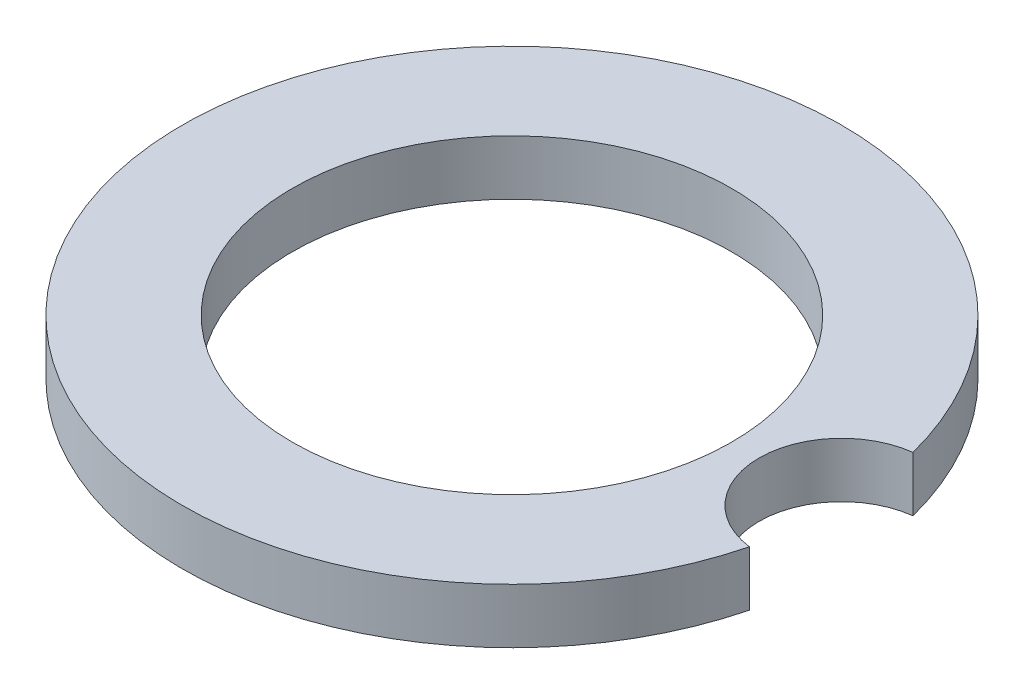
SolidWorks part; units mm, degrees
ref_plane "Front Plane" through (0, 0, 0) normal (0, 0, 1) x (1, 0, 0)
ref_plane "Top Plane" through (0, 0, 0) normal (0, 1, 0) x (1, 0, 0)
ref_plane "Right Plane" through (0, 0, 0) normal (1, 0, 0) x (0, 0, -1)
sketch "Sketch1" plane through (0, 0, 0) normal (0, 1, 0) x (1, 0, 0)
  circle A0 centre (0, 0) radius 50.8
  circle A1 centre (0, 0) radius 76.1746
  dimension "Front_CR_ID" = 101.6
  dimension "Front_CR_OD" = 152.3492
extrude "Boss-Extrude1" add sketch "Sketch1" along normal blind 12.7 contours A1
extrude "Cut-Extrude2" cut sketch "Sketch1<10>" along normal through all contours A0
sketch "Sketch1<10>" plane through (0, 0, 0) normal (0, 1, 0) x (1, 0, 0) same geometry as "Sketch1"
sketch "Sketch2" plane through (0, 12.7, 0) normal (0, 1, 0) x (1, 0, 0)
  line L0 (76.2, 19.05) -> (76.2, -19.05)
  arc A0 (76.2, 19.05) -> (76.2, -19.05) centre (76.1746, 0) ccw
  circle A1 centre (0, 0) radius 76.1746 construction
  dimension "D1" = 38.1
extrude "Cut-Extrude3" cut sketch "Sketch2" against normal through all contours A0 L0
ref_plane "Plane1" through (0, 6.35, 0) normal (0, -1, 0) x (-1, 0, 0)
equation "\"Bodytube_OD\" = 6.17in"
equation "\"Bodytube_ID\" = 5.998in"
equation "\"Motor_OD\" = 4in"
equation "\"Fwd_Tube_Length\" = 38in"
equation "\"Mid_Tube_Length\" = 8in"
equation "\"Aft_Section_Length\"= 40in"
equation "\"Mid_Coupler_Length\"= 13in"
equation "\"Aft_Lower_Length\"= 22in"
equation "\"AB_Coupler_OD_Length\"= 1in"
equation "\"AB_Coupling_Section_Length\"= 0.375in"
equation "\"AB_Coupler_Length\"= \"AB_Coupler_OD_Length\" + \"AB_Coupling_Section_Length\" * 2"
equation "\"Cutout_Angle\" = 80"
equation "\"AB_Paddle_Height\" = 0.375in"
equation "\"AB_Coupler_Num_Screws\"= 6"
equation "\"Num_Cutouts\" = 3"
equation "\"AB_Coupler_OD\"= 6.17in"
equation "\"AB_Coupler_ID\"= 5.75in"
equation "\"AB_Coupler_Surface_Diameter\"= 5.998in"
equation "\"AB_Coupling_Screw_Diameter\"= 0.1065in"
equation "\"AB_Central_Bushing_Length\" = .75in"
equation "\"Lead_Screw_Dist\" = 2.25in"
equation "\"Lead_Screw_Diam\" = (27/64)*1in"
equation "\"Lead_Screw_Length\" = (\"Mid_Coupler_Length\" + 2*0.375in + 2*0.5in)"
equation "\"Paddle_Pin_Offset\" = .25in"
equation "\"Paddle_Pin_Radius\" = 2.25in"
equation "\"Paddle_Gear_OD\" = 3.2in"
equation "\"Fwd_BKHD_From_Top\" = 18in"
equation "\"Front_CR_OD@Sketch1\"=\"Bodytube_ID\""
equation "\"Front_CR_ID@Sketch1\"=\"Motor_OD\""
